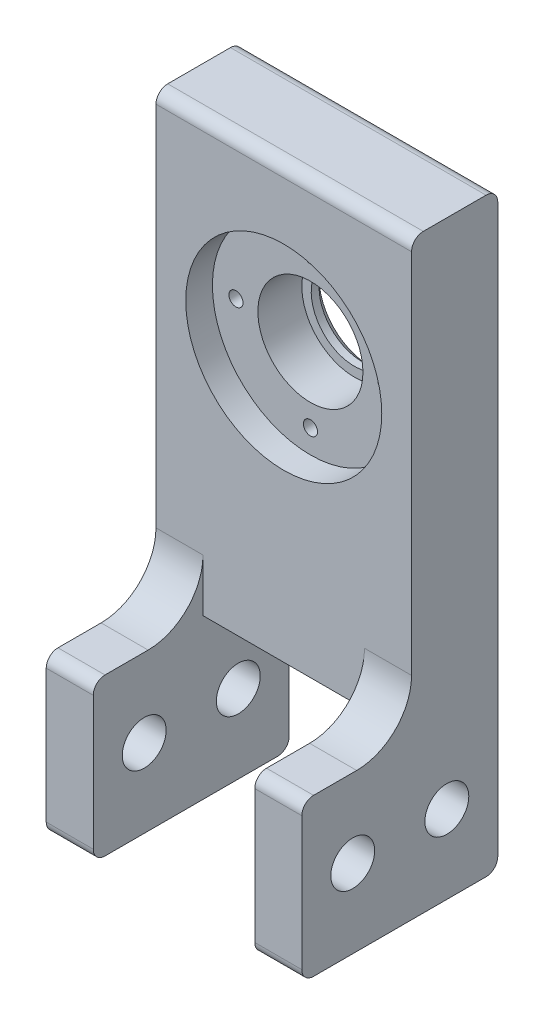
SolidWorks part; units mm, degrees
ref_plane "Front plane" through (0, 0, 0) normal (0, 0, 1) x (1, 0, 0)
ref_plane "Top plane" through (0, 0, 0) normal (0, 1, 0) x (1, 0, 0)
ref_plane "Right plane" through (0, 0, 0) normal (1, 0, 0) x (0, 0, -1)
ref_axis "Axis X" through (0, 0, 0) along (1, 0, 0)
ref_axis "Axis Y" through (0, 0, 0) along (0, 1, 0)
ref_axis "Axis Z" through (0, 0, 0) along (0, 0, 1)
sketch "Sketch1" plane through (0, 0, 0) normal (1, 0, 0) x (0, 0, -1)
  line L1 (5.5, 65.3) -> (-5.5, 65.3)
  line L2 (5.5, 65.3) -> (5.5, 10.3)
  line L3 (5.5, 10.3) -> (-5.5, 10.3)
  line L4 (-5.5, 65.3) -> (-5.5, 10.3)
  line L5 (5.5, 65.3) -> (-5.5, 10.3) construction
  line L6 (5.5, 10.3) -> (-5.5, 65.3) construction
  point P0 (0, 37.8)
  dimension "D1" = 10.3
  dimension "D2" = 11
  dimension "D3" = 55
extrude "Extrude1" add sketch "Sketch1" along normal blind 10.3 and the other way blind 10.3
sketch "Sketch2" plane through (10.3, 0, 0) normal (1, 0, 0) x (0, 0, -1)
  line L0 (5.5, 10.3) -> (5.5, 65.3) construction
  line L1 (19.5, 10) -> (12.5, 10) construction
  line L2 (19.5, 10) -> (19.5, -10) construction
  line L3 (19.5, -10) -> (-19.5, -10) construction
  line L4 (-19.5, 10) -> (-19.5, -10)
  line L5 (19.5, 10) -> (-19.5, -10) construction
  line L6 (19.5, -10) -> (-19.5, 10) construction
  line L7 (-5.5, 65.3) -> (5.5, 65.3)
  line L8 (-5.5, 65.3) -> (-5.5, 17)
  line L9 (-5.5, 10) -> (5.5, 10) construction
  line L10 (5.5, 65.3) -> (5.5, 17)
  line L11 (-12.5, 10) -> (-19.5, 10)
  line L12 (5.5, 10) -> (-5.5, 10) construction
  line L13 (5.5, 17) -> (5.5, -10)
  line L14 (-19.5, -10) -> (5.5, -10)
  arc A0 (12.5, 10) -> (5.5, 17) centre (12.5, 17) cw construction
  arc A1 (-12.5, 10) -> (-5.5, 17) centre (-12.5, 17) ccw
  point P0 (0, 0)
  dimension "D3" = 7
  dimension "D1" = 20
  dimension "D2" = 25
extrude "Extrude2" add sketch "Sketch2" along normal blind 6
mirror "Mirror2" about plane through (0, 0, 0) normal (1, 0, 0) of "Extrude2"
sketch "Sketch5" plane through (0, 0, 5.5) normal (0, 0, 1) x (1, 0, 0)
  line L0 (-16.3, 19.5) -> (16.3, 19.5) construction
  line L1 (-16.3, 65.3) -> (-16.3, 17) construction
  line L2 (16.3, 65.3) -> (16.3, 17) construction
  line L3 (-16.3, 22.3) -> (16.3, 22.3) construction
  line L4 (-16.3, 16.7) -> (16.3, 16.7) construction
  line L5 (-16.3, 54.55) -> (16.3, 54.55) construction
  line L6 (-16.3, 51.75) -> (16.3, 51.75) construction
  line L7 (-16.3, 48.95) -> (16.3, 48.95) construction
  line L8 (-5.5, 44) -> (5.5, 44) construction
  line L9 (-10.3, 10) -> (10.3, 10) construction
  line L10 (-10.3, 10) -> (-10.3, -10) construction
  line L11 (10.3, 10) -> (10.3, -10) construction
  circle A0 centre (0, 44) radius 5.5
  dimension "D5" = 11
  dimension "D1" = 5.6
  dimension "D2" = 5.6
  dimension "D3" = 19.5
  dimension "D4" = 32.25
  dimension "D7" = 10
  dimension "D8" = 34
extrude "Extrude4" cut sketch "Sketch5" against normal through all
sketch "Эскиз1" plane through (16.3, 0, 0) normal (1, 0, 0) x (0, 0, -1)
  line L0 (-19.5, 0) -> (5.5, 0) construction
  line L1 (-19.5, 10) -> (-19.5, -10) construction
  line L2 (5.5, -10) -> (5.5, 65.3) construction
  line L3 (-7, 0) -> (-7, 8.1058) construction
  circle A0 centre (-13, 0) radius 2.8
  circle A2 centre (-1, 0) radius 2.8
  dimension "D1" = 5.6
  dimension "D2" = 12
extrude "Вырез-Вытянуть1" cut sketch "Эскиз1" against normal through all
fillet "Fillet2" radius 1.5 8 edges at (13.3, 10, 19.5) (-13.3, 10, 19.5) (0, 65.3, 5.5) (0, 65.3, -5.5) (13.3, -10, -5.5) (-13.3, -10, -5.5) (-13.3, -10, 19.5) (13.3, -10, 19.5)
sketch "Эскиз4" plane through (0, 0, 5.5) normal (0, 0, 1) x (1, 0, 0)
  circle A0 centre (0, 44) radius 6.7
  dimension "D1" = 13.4
extrude "Вырез-Вытянуть2" cut sketch "Эскиз4" against normal offset from surface (9 mm away) 2 up to face at (5.5, 44, -5.5)
sketch "Эскиз5" plane through (0, 0, 5.5) normal (0, 0, 1) x (1, 0, 0)
  circle A0 centre (0, 44) radius 12.5
  dimension "D1" = 25
extrude "Вырез-Вытянуть3" cut sketch "Эскиз5" against normal offset from surface (3.4 mm away) 5.6 up to face at (0, 50.7, -3.5)
sketch "Эскиз6" plane through (0, 0, 2.1) normal (0, 0, 1) x (1, 0, 0)
  circle A0 centre (0, 44) radius 9.5 construction
  circle A1 centre (0, 53.5) radius 0.9
  circle A2 centre (9.5, 44) radius 0.9
  circle A3 centre (0, 34.5) radius 0.9
  circle A4 centre (-9.5, 44) radius 0.9
  point P5 (0, 0)
  point P6 (0, 0)
  dimension "D1" = 19
  dimension "D2" = 1.8
  dimension "D3" = 4
extrude "Вырез-Вытянуть4" cut sketch "Эскиз6" against normal blind 7
chamfer "Фаска1" distance 1 angle 45 1 edges at (5.5, 44, -5.5)
equation "\"bearing_d1\"= 5"
equation "\"bearing_d2\"= 10"
equation "\"print_offset\"= 0.6"
equation "\"bearing_h\"=15"
equation "\"prof_width\"= 20'Aluminium profile parameters"
equation "\"prof_groove\"= 6"
equation "\"prof_length\"= 410"
equation "\"prof_screw_diameter\"= 4"
equation "\"screw2_diameter\"= 2"
equation "\"screw2_diameter_ext\"= 4"
equation "\"screw2_heigh_head\"= 2"
equation "\"nut2_diameter\"= 4"
equation "\"nut2_heigh\"= 2"
equation "\"screw_offset_ext\"= 2"
equation "\"angle_heigh\"= 50'Angle mount parameters"
equation "\"angle_thikness\"= 3"
equation "\"angle_width\"= 30"
equation "\"mount_thikness\"= 15'Other mounts parameters"
equation "\"mount_screw\"= 4"
equation "\"mount_screw_distance\"= 40"
equation "\"bearings_distance\"= 22"
equation "\"tape_distance\"= 7.35"
equation "\"bearing_grove_d1\"= 4"
equation "\"bearing_grove_d2\"= 13"
equation "\"bearing_grove_h\"= 4"
equation "\"bearing_groove_r\"= 1"
equation "\"D1@Sketch1\"=(\"prof_width\"+\"print_offset\")/2"
equation "\"D1@Extrude1\"=(\"prof_width\"+\"print_offset\")/2"
equation "\"D2@Extrude1\"=(\"prof_width\"+\"print_offset\")/2"
equation "\"D1@Sketch2\"=\"prof_width\""
equation "\"D2@Sketch5\"= \"D1@Sketch5\""
equation "\"D7@Sketch5\"=\"prof_width\"/2"
equation "\"D1@Эскиз1\"=\"print_offset\"+5"
equation "\"D1@Эскиз4\"=\"print_offset\"/3*2+13"
equation "\"D1@Вырез-Вытянуть3\"=\"print_offset\"+5"
equation "\"radial_bearing_d1\"= 6"
equation "\"radial_bearing_d2\"= 13"
equation "\"radial_bearing_h\"= 5"
equation "\"shaft_d\"= 6"
equation "\"shaft_h\"= 50"
equation "\"central_hole_d\"= 20"
equation "\"sitting_screws_d\"= 30"
equation "\"screw_d\"= 2"
equation "\"screw_hh_d\"= 3.4"
equation "\"screw_h\"= 8"
equation "\"screw_hh_h\"= 2"
equation "\"motor_screw_d\"= 4"
equation "\"motor_screw_hh_d\"= 7.4"
equation "\"motor_screw_h\"= 20"
equation "\"motor_screw_hh_h\"= 2.5"
equation "\"motor_nut_d\"= 6.8"
equation "\"motor_nut_h\"= 2.8"
equation "\"nut_d\"= 3.9"
equation "\"nut_h\"= 2"
equation "\"washer_d1\"= 20.3"
equation "\"washer_d2\"= 44"
equation "\"washer_h\"= 4.45"
